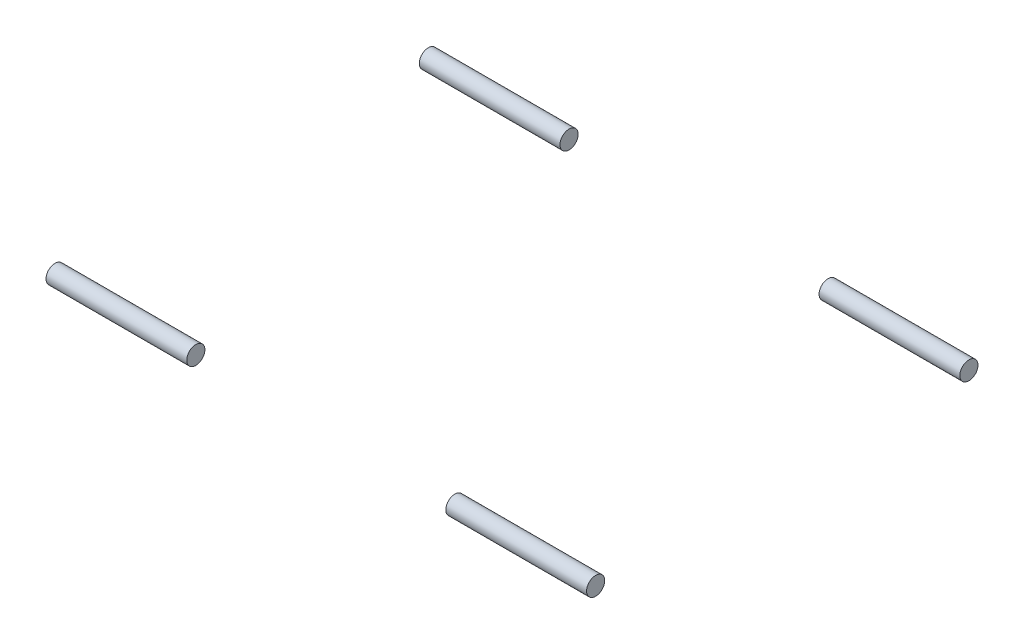
SolidWorks part; units mm, degrees
material "6061-T6 (SS)"
ref_plane "Front Plane" through (0, 0, 0) normal (0, 0, 1) x (1, 0, 0)
ref_plane "Top Plane" through (0, 0, 0) normal (0, 1, 0) x (1, 0, 0)
ref_plane "Right Plane" through (0, 0, 0) normal (1, 0, 0) x (0, 0, -1)
sketch "Sketch1" plane through (94.5, 0, 0) normal (-1, 0, 0) x (0, 0, 1)
  circle A0 centre (130.5, 0) radius 3.175
  circle A1 centre (0, 0) radius 3.175
  circle A2 centre (0, 0) radius 3.175 construction
  circle A3 centre (130.5, 0) radius 3.175 construction
extrude "Boss-Extrude1" add sketch "Sketch1" along normal up to surface (49.2125 mm away)
mirror "Mirror1" about plane through (0, 0, 0) normal (1, 0, 0) of bodies 101 102
